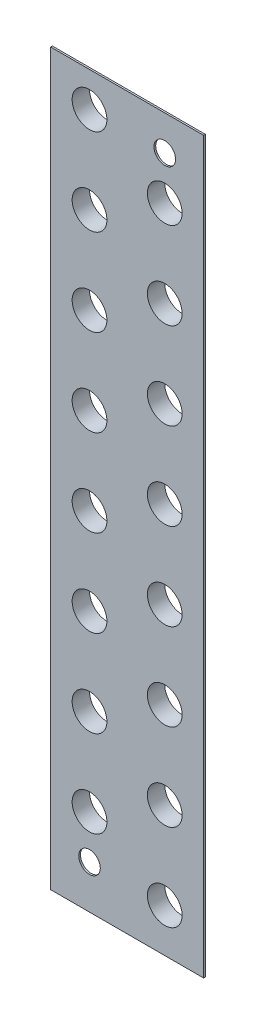
SolidWorks part; units mm, degrees
material "201 Annealed Stainless Steel (SS)"
ref_plane "Front Plane" through (0, 0, 0) normal (0, 0, 1) x (1, 0, 0)
ref_plane "Top Plane" through (0, 0, 0) normal (0, 1, 0) x (1, 0, 0)
ref_plane "Right Plane" through (0, 0, 0) normal (1, 0, 0) x (0, 0, -1)
sketch "Sketch1" plane through (0, 0, 0) normal (0, 0, 1) x (1, 0, 0)
  line L1 (-22, -105) -> (22, -105)
  line L2 (-22, -105) -> (-22, 105)
  line L3 (-22, 105) -> (22, 105)
  line L4 (22, -105) -> (22, 105)
  line L5 (-22, -105) -> (22, 105) construction
  line L6 (-22, 105) -> (22, -105) construction
  point P0 (0, 0)
  dimension "D1" = 44
  dimension "D2" = 210
extrude "Boss-Extrude1" add sketch "Sketch1" along normal blind 0.5
ref_axis "Axis1" through (0, 0, -111.0259) along (0, 0, 1)
sketch "Sketch7" plane through (0, 0, 0.5) normal (0, 0, 1) x (1, 0, 0)
  line L0 (0, 105) -> (0, 50105) construction
  line L1 (22, 105) -> (-22, 105) construction
  line L2 (36.3565, 95) -> (-49963.6435, 95) construction
  line L3 (39.5295, 82.5) -> (-49960.4705, 82.5) construction
  line L4 (10.8253, 82.5) -> (10.8253, -49917.5) construction
  circle A0 centre (10.8253, 82.5) radius 5
  circle A1 centre (-10.8253, 95) radius 5
  point P4 (0, 105)
  point P9 (10.8253, 95)
  point P10 (-10.8253, 95)
  point P11 (10.8253, 82.5)
  dimension "D4" = 10
  dimension "D1" = 10
  dimension "D2" = 22.5
  dimension "D3" = 25
extrude "Cut-Extrude3" cut sketch "Sketch7" against normal through all
pattern_linear "LPattern1" count 8 spacing 25 along (0, -1, 0) of "Cut-Extrude3"
sketch "Sketch8" plane through (0, 0, 0) normal (0, 0, -1) x (-1, 0, 0)
  line L1 (10.2106, -92.5) -> (-49989.7894, -92.5) construction
  line L2 (10.8253, -92.5771) -> (10.8253, 49907.4229) construction
  line L3 (-10.8253, 96.0482) -> (-10.8253, -49903.9518) construction
  line L4 (-9.4352, 95) -> (49990.5648, 95) construction
  circle A0 centre (-10.8253, 95) radius 3.1
  circle A1 centre (10.8253, -92.5) radius 3.1
  dimension "D1" = 6.2
  dimension "D2" = 6.2
extrude "Cut-Extrude4" cut sketch "Sketch8" against normal through all
sketch "Sketch10" plane through (0, 0, 0) normal (0, 0, -1) x (-1, 0, 0)
  circle A3 centre (-10.8253, -92.5) radius 5.5
  circle A4 centre (-10.8253, -92.5) radius 5.5
  circle A5 centre (-10.8253, -92.5) radius 5 construction
  circle A6 centre (10.8253, -80) radius 5.5
  circle A7 centre (10.8253, -80) radius 5.5
  circle A8 centre (-10.8253, -92.5) radius 5
  circle A9 centre (10.8253, -80) radius 5 construction
  circle A10 centre (10.8253, -80) radius 5
  dimension "D1" = 0.5
  dimension "D2" = 0.5
extrude "Boss-Extrude3" add sketch "Sketch10" along normal blind 4.5
fillet "Fillet2" radius 0.5 2 edges at (-16.3253, -80, 0) (5.3253, -92.5, 0)
pattern_linear "LPattern3" count 8 spacing 25 along (0, 1, 0) of "Fillet2", "Boss-Extrude3"
